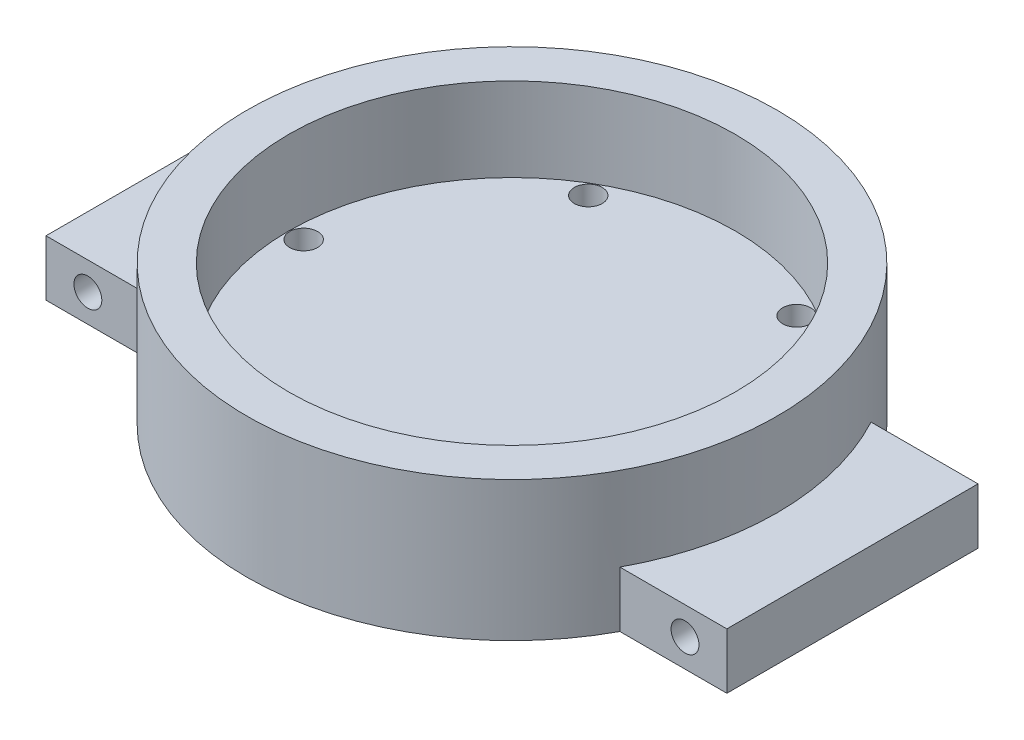
SolidWorks part; units mm, degrees
ref_plane "Front Plane" through (0, 0, 0) normal (0, 0, 1) x (1, 0, 0)
ref_plane "Top Plane" through (0, 0, 0) normal (0, 1, 0) x (1, 0, 0)
ref_plane "Right Plane" through (0, 0, 0) normal (1, 0, 0) x (0, 0, -1)
sketch "Sketch7" plane through (0, 0, 0) normal (0, 1, 0) x (1, 0, 0)
  line L1 (-61, 0) -> (61, 0)
  line L2 (-61, 0) -> (-61, 45)
  line L3 (-61, 45) -> (61, 45)
  line L4 (61, 0) -> (61, 45)
  dimension "D1" = 45
  dimension "D2" = 122
extrude "Boss-Extrude1" add sketch "Sketch7" along normal blind 10
sketch "Sketch9" plane through (0, 10, 0) normal (0, 1, 0) x (1, 0, 0)
  line L0 (-61, 45) -> (-61, 0) construction
  circle A0 centre (0, 22.5) radius 37.333 construction
  circle A1 centre (0, 22.5) radius 42.333
  circle A2 centre (-37.333, 22.5) radius 2.5
  circle A3 centre (-18.6665, 54.8313) radius 2.5
  circle A4 centre (18.6665, 54.8313) radius 2.5
  circle A5 centre (37.333, 22.5) radius 2.5
  circle A6 centre (18.6665, -9.8313) radius 2.5
  circle A7 centre (-18.6665, -9.8313) radius 2.5
  point P6 (-61, 22.5)
  dimension "D1" = 74.666
  dimension "D2" = 5
  dimension "D3" = 5
  dimension "D4" = 6
extrude "Boss-Extrude2" add sketch "Sketch9" against normal up to surface (10 mm away) up to face at (0, 0, -22.5)
extrude "Cut-Extrude4" cut sketch "Sketch9<2>" against normal through all contours A2 | A5
sketch "Sketch9<2>" plane through (0, 10, 0) normal (0, 1, 0) x (1, 0, 0) same geometry as "Sketch9"
sketch "Sketch10" plane through (0, 0, 0) normal (0, -1, 0) x (1, 0, 0)
  circle A0 centre (0, -22.5) radius 40
  arc A1 (35.8585, 0) -> (-35.8585, 0) centre (0, -22.5) ccw construction
  circle A2 centre (0, -22.5) radius 47.5
  line M5 (-61, -45) -> (-35.8585, -45)
  arc M6 (-35.8585, -45) -> (35.8585, -45) centre (0, -22.5) ccw
  line M7 (35.8585, -45) -> (61, -45)
  line M9 (61, 0) -> (35.8585, 0)
  arc M10 (35.8585, 0) -> (-35.8585, 0) centre (0, -22.5) ccw
  line M11 (-35.8585, 0) -> (-61, 0)
  dimension "D1" = 80
  dimension "D2" = 7.5
extrude "Boss-Extrude3" add sketch "Sketch10" against normal blind 25 contours A2 M5 M7 M6 | A2 A0 M7 M9 M10 M11 M5 M6 | A2 M9 M11 M10 | A2 | A0 region at (44.8275, 0, -33.7905) region at (38.8458, 0, 0.8732) region at (0, 0, -69.1268)
sketch "Sketch11" plane through (0, 0, 0) normal (0, 0, 1) x (1, 0, 0)
  line L0 (61, 10) -> (61, 0) construction
  line L1 (-61, 10) -> (-61, 0) construction
  circle A0 centre (-53.5, 5) radius 2.5
  circle A1 centre (53.5, 5) radius 2.5
  point P8 (-61, 5)
  dimension "D2" = 5
  dimension "D1" = 7.5
  dimension "D3" = 7.5
extrude "Cut-Extrude5" cut sketch "Sketch11" against normal through all
